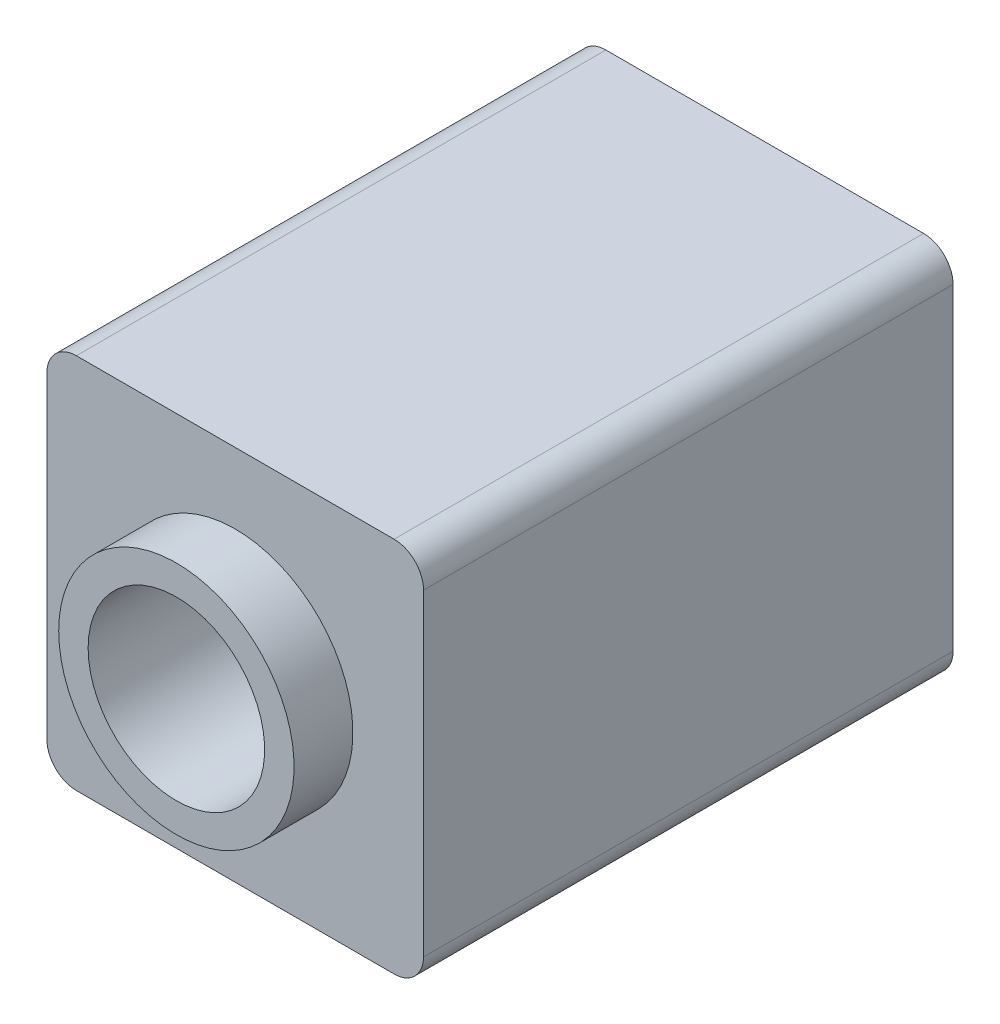
SolidWorks part; units mm, degrees
ref_plane "Front Plane" through (0, 0, 0) normal (0, 0, 1) x (1, 0, 0)
ref_plane "Top Plane" through (0, 0, 0) normal (0, 1, 0) x (1, 0, 0)
ref_plane "Right Plane" through (0, 0, 0) normal (1, 0, 0) x (0, 0, -1)
sketch "Sketch2" plane through (0, 0, -57.4655) normal (0, 0, -1) x (-1, 0, 0)
  line L1 (-6.4405, -35.0284) -> (-1.0405, -35.0284)
  line L2 (-6.9405, -34.5284) -> (-6.9405, -29.1284)
  line L3 (-6.4405, -28.6284) -> (-1.0405, -28.6284)
  line L4 (-0.5405, -34.5284) -> (-0.5405, -29.1284)
  line L5 (-6.9405, -35.0284) -> (-0.5405, -28.6284) construction
  line L6 (-6.9405, -28.6284) -> (-0.5405, -35.0284) construction
  circle A0 centre (-3.7405, -31.8284) radius 1.5
  arc A1 (-0.5405, -34.5284) -> (-1.0405, -35.0284) centre (-1.0405, -34.5284) cw
  arc A2 (-6.9405, -34.5284) -> (-6.4405, -35.0284) centre (-6.4405, -34.5284) ccw
  arc A3 (-6.9405, -29.1284) -> (-6.4405, -28.6284) centre (-6.4405, -29.1284) cw
  arc A4 (-0.5405, -29.1284) -> (-1.0405, -28.6284) centre (-1.0405, -29.1284) ccw
  point P0 (-3.7405, -31.8284)
  dimension "D2" = 3
  dimension "D3" = 0.5
  dimension "D1" = 6.4
extrude "Boss-Extrude1" add sketch "Sketch2" along normal blind 10
sketch "Sketch3" plane through (0, 0, -57.4655) normal (0, 0, -1) x (-1, 0, 0)
  line L4 (-1.0405, -28.6284) -> (-6.4405, -28.6284)
  line L5 (-6.9405, -29.1284) -> (-6.9405, -34.5284)
  line L6 (-6.4405, -35.0284) -> (-1.0405, -35.0284)
  line L7 (-0.5405, -34.5284) -> (-0.5405, -29.1284)
  line L8 (-1.0405, -28.6284) -> (-6.4405, -28.6284)
  line L9 (-6.9405, -29.1284) -> (-6.9405, -34.5284)
  line L10 (-6.4405, -35.0284) -> (-1.0405, -35.0284)
  line L11 (-0.5405, -34.5284) -> (-0.5405, -29.1284)
  circle A1 centre (-3.7405, -31.8284) radius 5 construction
  circle A2 centre (-3.7405, -31.8284) radius 2
  arc A6 (-6.4405, -28.6284) -> (-6.9405, -29.1284) centre (-6.4405, -29.1284) ccw
  arc A7 (-6.9405, -34.5284) -> (-6.4405, -35.0284) centre (-6.4405, -34.5284) ccw
  arc A8 (-1.0405, -35.0284) -> (-0.5405, -34.5284) centre (-1.0405, -34.5284) ccw
  arc A9 (-0.5405, -29.1284) -> (-1.0405, -28.6284) centre (-1.0405, -29.1284) ccw
  arc A10 (-6.4405, -28.6284) -> (-6.9405, -29.1284) centre (-6.4405, -29.1284) ccw
  arc A11 (-6.9405, -34.5284) -> (-6.4405, -35.0284) centre (-6.4405, -34.5284) ccw
  arc A12 (-1.0405, -35.0284) -> (-0.5405, -34.5284) centre (-1.0405, -34.5284) ccw
  arc A13 (-0.5405, -29.1284) -> (-1.0405, -28.6284) centre (-1.0405, -29.1284) ccw
  dimension "D1" = 4
  dimension "D2" = 0
extrude "Cut-Extrude1" cut sketch "Sketch3" along normal blind 1
sketch "Sketch4" plane through (0, 0, -67.4655) normal (0, 0, -1) x (-1, 0, 0)
  circle A0 centre (-3.7405, -31.8284) radius 2.4
extrude "Cut-Extrude2" cut sketch "Sketch4" against normal blind 4
